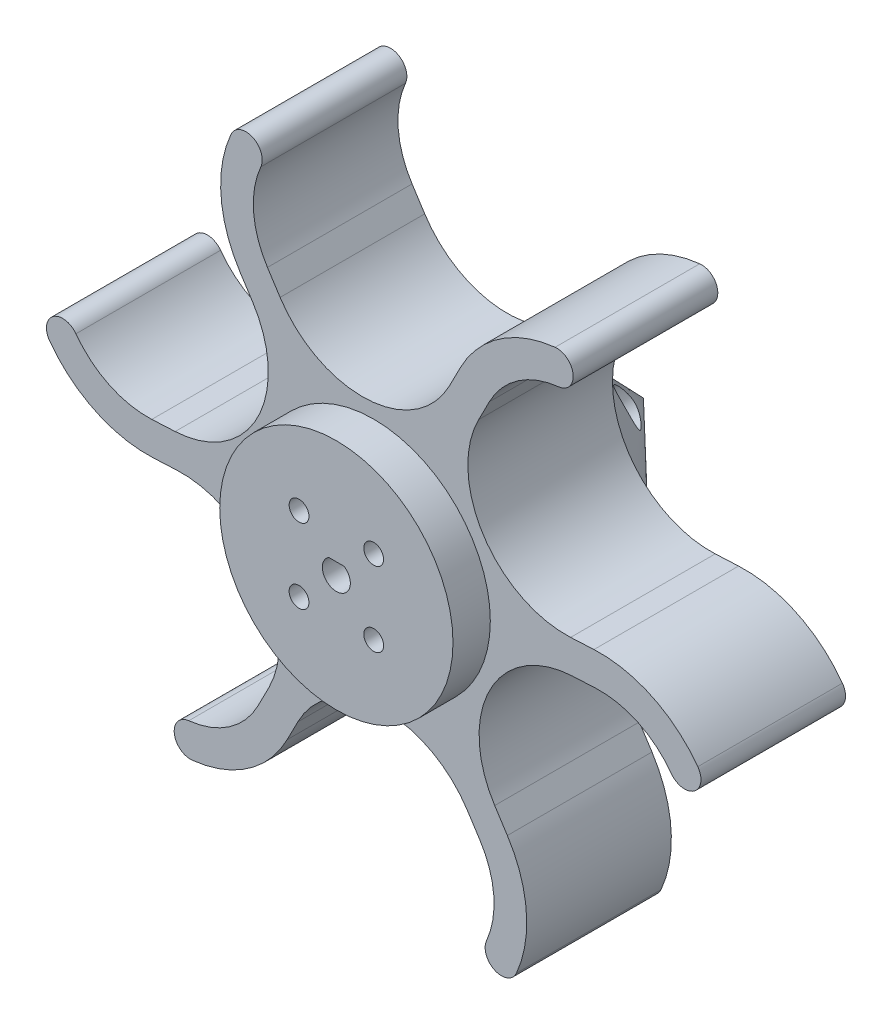
SolidWorks part; units mm, degrees
ref_plane "Front Plane" through (0, 0, 0) normal (0, 0, 1) x (1, 0, 0)
ref_plane "Top Plane" through (0, 0, 0) normal (0, 1, 0) x (1, 0, 0)
ref_plane "Right Plane" through (0, 0, 0) normal (1, 0, 0) x (0, 0, -1)
sketch "Sketch1" plane through (0, 0, 0) normal (0, 0, 1) x (1, 0, 0)
  line L0 (-33.6058, 45.6534) -> (-25.9397, 33.7658)
  line L1 (-30.6644, 47.5503) -> (-56.5119, -2.781) construction
  line L2 (-56.5119, -2.781) -> (-25.8475, -50.3313) construction
  line L3 (-25.8475, -50.3313) -> (30.6644, -47.5503) construction
  line L4 (30.6644, -47.5503) -> (56.5119, 2.781) construction
  line L5 (56.5119, 2.781) -> (25.8475, 50.3313) construction
  line L6 (25.8475, 50.3313) -> (-30.6644, 47.5503) construction
  line L7 (-27.723, 49.4471) -> (-20.0569, 37.5596)
  line L8 (22.7341, 51.9302) -> (16.2722, 39.3474)
  line L9 (28.961, 48.7324) -> (22.4991, 36.1496)
  line L10 (56.3399, 6.2768) -> (42.2119, 5.5815)
  line L11 (56.684, -0.7147) -> (42.556, -1.41)
  line L12 (33.6058, -45.6534) -> (25.9397, -33.7658)
  line L13 (27.723, -49.4471) -> (20.0569, -37.5596)
  line L14 (-22.7341, -51.9302) -> (-16.2722, -39.3474)
  line L15 (-28.961, -48.7324) -> (-22.4991, -36.1496)
  line L16 (-56.3399, -6.2768) -> (-42.2119, -5.5815)
  line L17 (-56.684, 0.7147) -> (-42.556, 1.41)
  circle A0 centre (41.1797, 26.5562) radius 21 construction
  circle A1 centre (43.5882, -22.3846) radius 21 construction
  circle A2 centre (2.4085, -48.9408) radius 21 construction
  circle A3 centre (-41.1797, -26.5562) radius 21 construction
  circle A4 centre (-43.5882, 22.3846) radius 21 construction
  circle A5 centre (-2.4085, 48.9408) radius 21 construction
  circle A6 centre (0, 0) radius 49 construction
  circle A7 centre (-30.6644, 47.5503) radius 3.5
  circle A8 centre (25.8475, 50.3313) radius 3.5
  circle A9 centre (56.5119, 2.781) radius 3.5
  circle A10 centre (30.6644, -47.5503) radius 3.5
  circle A11 centre (-25.8475, -50.3313) radius 3.5
  circle A12 centre (-56.5119, -2.781) radius 3.5
  arc A13 (-42.556, 1.41) -> (-25.9397, 33.7658) centre (-43.5882, 22.3846) ccw
  arc A14 (-20.0569, 37.5596) -> (16.2722, 39.3474) centre (-2.4085, 48.9408) ccw
  arc A15 (22.4991, 36.1496) -> (42.2119, 5.5815) centre (41.1797, 26.5562) ccw
  arc A16 (42.556, -1.41) -> (25.9397, -33.7658) centre (43.5882, -22.3846) ccw
  arc A17 (20.0569, -37.5596) -> (-16.2722, -39.3474) centre (2.4085, -48.9408) ccw
  arc A18 (-22.4991, -36.1496) -> (-42.2119, -5.5815) centre (-41.1797, -26.5562) ccw
  point P25 (0, 0)
  point P36 (0, 0)
  point P60 (0, 0)
  point P77 (0, 0)
  dimension "D2" = 42
  dimension "D4" = 7
  dimension "D1" = 6
  dimension "D3" = 6
  dimension "D5" = 6
  dimension "D6" = 6
extrude "Boss-Extrude1" add sketch "Sketch1" along normal blind 21 contours A18 L15 A11 L14 A17 L13 A10 L12 A16 L11 A9 L10 A15 L9 A8 L8 A14 L7 A7 L0 A13 L17 A12 L16 | A12 | A7 | A8 | A9 | A10 | A11 region at (0, 0, 0) region at (-30.6644, 47.5503, 0) region at (-56.5119, -2.781, 0) region at (25.8475, 50.3313, 0) region at (-25.8475, -50.3313, 0) region at (56.5119, 2.781, 0) region at (30.6644, -47.5503, 0)
ref_plane "Plane1" through (0, 0, 0) normal (0.0492, -0.9988, 0) x (-0.9988, -0.0492, 0)
sketch "Sketch3" plane through (0, 0, 0) normal (0.0492, -0.9988, 0) x (-0.9988, -0.0492, 0)
  line L0 (0, 0) -> (-28, 0)
  line L1 (-28, 0) -> (0, 26.8135)
  line L2 (0, 26.8135) -> (0, 0)
  dimension "D1" = 28
revolve "Revolve1" add sketch "Sketch3" angle 360 about L2
sketch "Sketch4" plane through (0, 0, 21) normal (0, 0, 1) x (1, 0, 0)
  circle A0 centre (0, 0) radius 25
  dimension "D1" = 50
extrude "Boss-Extrude2" add sketch "Sketch4" along normal blind 18
sketch "Sketch5" plane through (0, 0, 39) normal (0, 0, 1) x (1, 0, 0)
  line L0 (-1.6583, 2.5) -> (1.6583, 2.5)
  arc A0 (-1.6583, 2.5) -> (1.6583, 2.5) centre (0, 0) ccw
  dimension "D1" = 6
  dimension "D2" = 2.5
extrude "Cut-Extrude2" cut sketch "Sketch5" against normal blind 20 contours A0 region at (0, -0.112, 39)
ref_plane "Plane2" through (-1.2288, 24.9698, 0) normal (-0.0492, 0.9988, 0) x (0.9988, 0.0492, 0)
ref_plane "Plane5" through (1.2288, -24.9698, 0) normal (0.0492, -0.9988, 0) x (-0.9988, -0.0492, 0)
sketch "Sketch7" plane through (0, 0, 39) normal (0, 0, 1) x (1, 0, 0)
  line L0 (0, 12.9158) -> (0, -15.3556) construction
  line L1 (-12.6694, 0) -> (16.084, 0) construction
  circle A0 centre (-8, 8) radius 2.125
  circle A1 centre (8, 8) radius 2.125
  circle A2 centre (8, -8) radius 2.125
  circle A3 centre (-8, -8) radius 2.125
  dimension "D1" = 4.25
  dimension "D2" = 8
  dimension "D3" = 8
extrude "Cut-Extrude3" cut sketch "Sketch7" against normal through all
sketch "Sketch9" plane through (0, 0, 0) normal (0, 0, -1) x (-1, 0, 0)
  line L0 (0, 0) -> (24.2952, 0) construction
  line L1 (0, 0) -> (0, 21.4598) construction
  circle A1 centre (-8, 8) radius 2.125 construction
  circle A5 centre (-8, 8) radius 2.125 construction
  circle A8 centre (-8, 8) radius 4
  circle A10 centre (8, 8) radius 4
  circle A11 centre (8, -8) radius 4
  circle A12 centre (-8, -8) radius 4
  dimension "D1" = 8
extrude "Cut-Extrude4" cut sketch "Sketch9" against normal offset from surface 3 and the other way through all up to face at (-10.125, -8, 39)
sketch "Sketch10" plane through (0, 0, 21) normal (0, 0, 1) x (1, 0, 0)
  line L0 (-1.6583, 2.5) -> (1.6583, 2.5) construction
  line L1 (-1.6583, 2.5) -> (1.6583, 2.5)
  line L12 (-22.4991, -36.1496) -> (-28.961, -48.7324)
  line L13 (-22.7341, -51.9302) -> (-16.2722, -39.3474)
  line L14 (20.0569, -37.5596) -> (27.723, -49.4471)
  line L15 (33.6058, -45.6534) -> (25.9397, -33.7658)
  line L16 (42.556, -1.41) -> (56.684, -0.7147)
  line L17 (56.3399, 6.2768) -> (42.2119, 5.5815)
  line L18 (22.4991, 36.1496) -> (28.961, 48.7324)
  line L19 (22.7341, 51.9302) -> (16.2722, 39.3474)
  line L20 (-20.0569, 37.5596) -> (-27.723, 49.4471)
  line L21 (-33.6058, 45.6534) -> (-25.9397, 33.7658)
  line L22 (-42.556, 1.41) -> (-56.684, 0.7147)
  line L23 (-56.3399, -6.2768) -> (-42.2119, -5.5815)
  line L24 (-22.4991, -36.1496) -> (-28.961, -48.7324)
  line L25 (-22.7341, -51.9302) -> (-16.2722, -39.3474)
  line L26 (20.0569, -37.5596) -> (27.723, -49.4471)
  line L27 (33.6058, -45.6534) -> (25.9397, -33.7658)
  line L28 (42.556, -1.41) -> (56.684, -0.7147)
  line L29 (56.3399, 6.2768) -> (42.2119, 5.5815)
  line L30 (22.4991, 36.1496) -> (28.961, 48.7324)
  line L31 (22.7341, 51.9302) -> (16.2722, 39.3474)
  line L32 (-20.0569, 37.5596) -> (-27.723, 49.4471)
  line L33 (-33.6058, 45.6534) -> (-25.9397, 33.7658)
  line L34 (-42.556, 1.41) -> (-56.684, 0.7147)
  line L35 (-56.3399, -6.2768) -> (-42.2119, -5.5815)
  circle A0 centre (8, -8) radius 2.125 construction
  arc A1 (-1.6583, 2.5) -> (1.6583, 2.5) centre (0, 0) ccw construction
  circle A2 centre (-8, -8) radius 2.125 construction
  circle A3 centre (8, 8) radius 2.125 construction
  circle A4 centre (-8, 8) radius 2.125 construction
  circle A5 centre (8, -8) radius 2.125
  arc A6 (-1.6583, 2.5) -> (1.6583, 2.5) centre (0, 0) ccw
  circle A7 centre (-8, -8) radius 2.125
  circle A8 centre (8, 8) radius 2.125
  circle A9 centre (-8, 8) radius 2.125
  arc A12 (-22.4991, -36.1496) -> (-42.2119, -5.5815) centre (-41.1797, -26.5562) ccw
  arc A13 (-28.961, -48.7324) -> (-22.7341, -51.9302) centre (-25.8475, -50.3313) ccw
  arc A14 (20.0569, -37.5596) -> (-16.2722, -39.3474) centre (2.4085, -48.9408) ccw
  arc A15 (27.723, -49.4471) -> (33.6058, -45.6534) centre (30.6644, -47.5503) ccw
  arc A16 (42.556, -1.41) -> (25.9397, -33.7658) centre (43.5882, -22.3846) ccw
  arc A17 (56.684, -0.7147) -> (56.3399, 6.2768) centre (56.5119, 2.781) ccw
  arc A18 (22.4991, 36.1496) -> (42.2119, 5.5815) centre (41.1797, 26.5562) ccw
  arc A19 (28.961, 48.7324) -> (22.7341, 51.9302) centre (25.8475, 50.3313) ccw
  arc A20 (-20.0569, 37.5596) -> (16.2722, 39.3474) centre (-2.4085, 48.9408) ccw
  arc A21 (-27.723, 49.4471) -> (-33.6058, 45.6534) centre (-30.6644, 47.5503) ccw
  arc A22 (-42.556, 1.41) -> (-25.9397, 33.7658) centre (-43.5882, 22.3846) ccw
  arc A23 (-56.684, 0.7147) -> (-56.3399, -6.2768) centre (-56.5119, -2.781) ccw
  arc A24 (-22.4991, -36.1496) -> (-42.2119, -5.5815) centre (-41.1797, -26.5562) ccw
  arc A25 (-28.961, -48.7324) -> (-22.7341, -51.9302) centre (-25.8475, -50.3313) ccw
  arc A26 (20.0569, -37.5596) -> (-16.2722, -39.3474) centre (2.4085, -48.9408) ccw
  arc A27 (27.723, -49.4471) -> (33.6058, -45.6534) centre (30.6644, -47.5503) ccw
  arc A28 (42.556, -1.41) -> (25.9397, -33.7658) centre (43.5882, -22.3846) ccw
  arc A29 (56.684, -0.7147) -> (56.3399, 6.2768) centre (56.5119, 2.781) ccw
  arc A30 (22.4991, 36.1496) -> (42.2119, 5.5815) centre (41.1797, 26.5562) ccw
  arc A31 (28.961, 48.7324) -> (22.7341, 51.9302) centre (25.8475, 50.3313) ccw
  arc A32 (-20.0569, 37.5596) -> (16.2722, 39.3474) centre (-2.4085, 48.9408) ccw
  arc A33 (-27.723, 49.4471) -> (-33.6058, 45.6534) centre (-30.6644, 47.5503) ccw
  arc A34 (-42.556, 1.41) -> (-25.9397, 33.7658) centre (-43.5882, 22.3846) ccw
  arc A35 (-56.684, 0.7147) -> (-56.3399, -6.2768) centre (-56.5119, -2.781) ccw
  dimension "D1" = 0
extrude "Boss-Extrude3" add sketch "Sketch10" along normal blind 10
sketch "Sketch11" plane through (0, 0, 0) normal (0, 0, -1) x (-1, 0, 0)
  line L0 (-56.3399, 6.2768) -> (-42.2119, 5.5815) construction
  line L1 (-56.684, -0.7147) -> (-42.556, -1.41) construction
  line L2 (-56.3399, 6.2768) -> (-42.2119, 5.5815)
  line L3 (-56.684, -0.7147) -> (-42.556, -1.41)
  line L4 (-42.556, -1.41) -> (-47.556, -1.1639)
  line L5 (-42.2119, 5.5815) -> (-47.2119, 5.8276)
  line L6 (-42.2119, 5.5815) -> (-42.556, -1.41)
  circle A0 centre (-56.5119, 2.781) radius 3.5 construction
  arc A1 (-25.9397, -33.7658) -> (-42.556, -1.41) centre (-43.5882, -22.3846) ccw construction
  circle A2 centre (-56.5119, 2.781) radius 3.5
  arc A3 (-25.9397, -33.7658) -> (-42.556, -1.41) centre (-43.5882, -22.3846) ccw
  arc A4 (-47.556, -1.1639) -> (-63.8237, -8.9217) centre (-48.4899, -20.141) ccw
  arc A5 (-47.2119, 5.8276) -> (-69.4731, -4.7883) centre (-48.4899, -20.141) ccw
  circle A6 centre (-66.6484, -6.855) radius 3.5
  circle A7 centre (0, 0) radius 72 construction
  circle A8 centre (0, 0) radius 67
  dimension "D2" = 19
  dimension "D4" = 144
  dimension "D3" = 7
  dimension "D1" = 5
  dimension "D5" = 5
extrude "Boss-Extrude4" add sketch "Sketch11" against normal up to surface (31 mm away) contours A5 A8 A6 A4 L3 A2 | A8 A6 | A6 A8 | A2 A5 | L2 A5 A2 L3 L6 | A8 A5 A6 region at (47.9349, 2.2458, 0) region at (56.299, 2.1726, 0) region at (60.9105, -1.9943, 0) region at (67.6502, -3.0737, 0) region at (68.1096, -7.0052, 0) region at (65.1545, -6.7013, 0) up to face at (0, 0, 31)
sketch "Sketch12" plane through (0, 0, 0) normal (0, 0, -1) x (-1, 0, 0)
  line L0 (-56.3399, 6.2768) -> (-42.2119, 5.5815) construction
  line L1 (-56.3399, 6.2768) -> (-42.2119, 5.5815)
  arc A0 (-59.9894, 3.1777) -> (-69.4731, -4.7883) centre (-48.4899, -20.141) ccw construction
  circle A1 centre (-56.5119, 2.781) radius 3.5 construction
  arc A2 (-59.9894, 3.1777) -> (-69.4731, -4.7883) centre (-48.4899, -20.141) ccw
  circle A3 centre (-56.5119, 2.781) radius 3.5
  arc A4 (-69.4731, -4.7883) -> (-42.2119, 5.5815) centre (-50.5685, -13.468) cw
  arc A5 (-47.2119, 5.8276) -> (-69.4731, -4.7883) centre (-48.4899, -20.141) ccw construction
  arc A6 (-47.2119, 5.8276) -> (-69.4731, -4.7883) centre (-48.4899, -20.141) ccw
  arc M1 (-56.3399, 6.2768) -> (-59.9894, 3.1777) centre (-56.5119, 2.781) ccw
  arc M2 (-59.9894, 3.1777) -> (-69.4731, -4.7883) centre (-48.4899, -20.141) ccw
  line M9 (-42.2119, 5.5815) -> (-56.3399, 6.2768)
extrude "Cut-Extrude5" cut sketch "Sketch12" against normal up to surface (31 mm away) contours A4 A3 M2 | A6 A3 M1 | A6 L1 A3 | A4 L1 M1 M9 region at (49.6027, 6.492, 0) region at (52.8771, 5.8376, 0) region at (57.308, 5.0557, 0) region at (63.5681, 1.6312, 0) up to face at (-5.875, 8, 31)
pattern_circular "CirPattern1" count 6 every 60 about axis through (0, 0, 0) along (0, 0, -1) of "Boss-Extrude4", "Cut-Extrude5"
